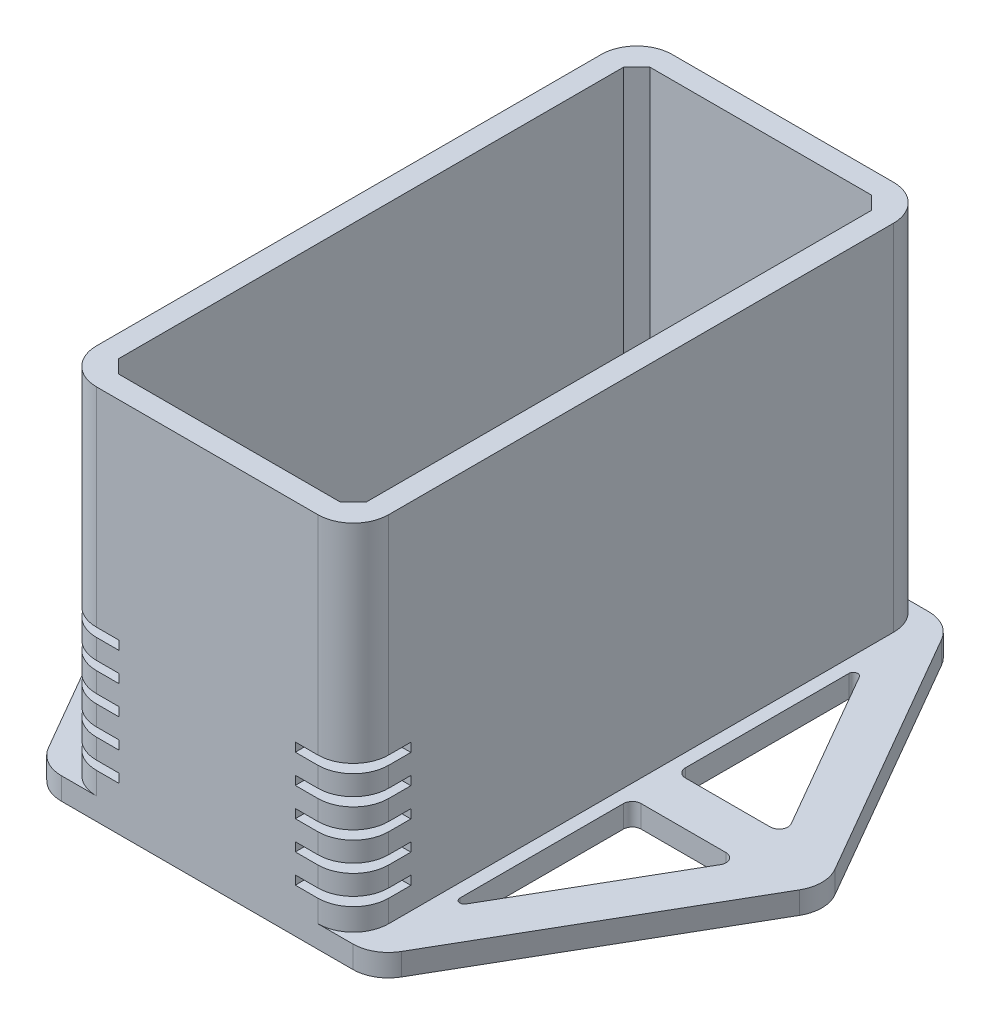
SolidWorks part; units mm, degrees
ref_plane "Front Plane" through (0, 0, 0) normal (0, 0, 1) x (1, 0, 0)
ref_plane "Top Plane" through (0, 0, 0) normal (0, 1, 0) x (1, 0, 0)
ref_plane "Right Plane" through (0, 0, 0) normal (1, 0, 0) x (0, 0, -1)
sketch "Sketch1" plane through (0, 0, 0) normal (0, 1, 0) x (1, 0, 0)
  line L1 (-75.0555, 0) -> (-37.5278, -65)
  line L2 (-37.5278, -65) -> (37.5278, -65)
  line L3 (37.5278, -65) -> (75.0555, 0)
  line L4 (75.0555, 0) -> (37.5278, 65)
  line L5 (37.5278, 65) -> (-37.5278, 65)
  line L6 (-37.5278, 65) -> (-75.0555, 0)
  circle A0 centre (0, 0) radius 65 construction
  circle A1 centre (0, 0) radius 50 construction
  dimension "D2" = 100
  dimension "D1" = 130
extrude "Boss-Extrude1" add sketch "Sketch1" along normal blind 5
fillet "Fillet1" radius 8 6 edges at (37.5278, 2.5, -65) (75.0555, 2.5, 0) (37.5278, 2.5, 65) (-37.5278, 2.5, 65) (-75.0555, 2.5, 0) (-37.5278, 2.5, -65)
sketch "Sketch3" plane through (0, 5, 0) normal (0, 1, 0) x (1, 0, 0)
  line L0 (-32.909, -65) -> (32.909, -65) construction
  line L1 (-25, 65) -> (25, 65)
  line L2 (-33, 57) -> (-33, -57)
  line L3 (-25, -65) -> (25, -65)
  line L4 (33, 57) -> (33, -57)
  line L5 (-33, 65) -> (33, -65) construction
  line L6 (-33, -65) -> (33, 65) construction
  arc A0 (33, 57) -> (25, 65) centre (25, 57) ccw
  arc A1 (33, -57) -> (25, -65) centre (25, -57) cw
  arc A2 (-25, -65) -> (-33, -57) centre (-25, -57) cw
  arc A3 (-25, 65) -> (-33, 57) centre (-25, 57) ccw
  point P0 (0, 0)
  dimension "D1" = 8
  dimension "D2" = 50
extrude "Boss-Extrude2" add sketch "Sketch3" along normal blind 80
sketch "Sketch4" plane through (0, 85, 0) normal (0, 1, 0) x (1, 0, 0)
  line L0 (-28, 57) -> (-25, 60)
  line L1 (25, 60) -> (28, 57)
  line L2 (28, -57) -> (25, -60)
  line L3 (-28, -57) -> (-25, -60)
  line L9 (-25, -60) -> (25, -60)
  line L10 (28, -57) -> (28, 57)
  line L11 (25, 60) -> (-25, 60)
  line L12 (-28, 57) -> (-28, -57)
  line L13 (-25, -60) -> (25, -60)
  line L14 (28, -57) -> (28, 57)
  line L15 (25, 60) -> (-25, 60)
  line L16 (-28, 57) -> (-28, -57)
  arc A9 (-28, -57) -> (-25, -60) centre (-25, -57) ccw
  arc A10 (25, -60) -> (28, -57) centre (25, -57) ccw
  arc A11 (28, 57) -> (25, 60) centre (25, 57) ccw
  arc A12 (-25, 60) -> (-28, 57) centre (-25, 57) ccw
  dimension "D1" = 5
extrude "Cut-Extrude1" cut sketch "Sketch4" against normal up to surface (85 mm away) up to face at (0, 0, 0)
sketch "Sketch8" plane through (0, 0, 0) normal (0, 1, 0) x (1, 0, 0)
  line L0 (0, 40) -> (0, 25) construction
  line L1 (0, 55) -> (0, 65) construction
  line L2 (9.5263, 26.5) -> (24.2487, 52) construction
  line L3 (22.5167, 55) -> (-22.5167, 55) construction
  line L4 (-24.2487, 52) -> (-9.5263, 26.5) construction
  line L5 (-12.5, 0) -> (-62.3346, 0) construction
  line L36 (6.9282, 25) -> (-6.9282, 25) construction
  line L37 (27.7128, 5) -> (57.1577, 5) construction
  line L38 (58.8897, 8) -> (36.3731, 47) construction
  line L39 (32.909, 47) -> (18.1865, 21.5) construction
  line L40 (25.1147, 6.5) -> (18.1865, 18.5) construction
  line L41 (18.1865, -21.5) -> (32.909, -47) construction
  line L42 (36.3731, -47) -> (58.8897, -8) construction
  line L43 (57.1577, -5) -> (27.7128, -5) construction
  line L44 (18.1865, -18.5) -> (25.1147, -6.5) construction
  line L45 (-9.5263, -26.5) -> (-24.2487, -52) construction
  line L46 (-22.5167, -55) -> (22.5167, -55) construction
  line L47 (24.2487, -52) -> (9.5263, -26.5) construction
  line L48 (-6.9282, -25) -> (6.9282, -25) construction
  line L49 (-27.7128, -5) -> (-57.1577, -5) construction
  line L50 (-58.8897, -8) -> (-36.3731, -47) construction
  line L51 (-32.909, -47) -> (-18.1865, -21.5) construction
  line L52 (-25.1147, -6.5) -> (-18.1865, -18.5) construction
  line L53 (-18.1865, 21.5) -> (-32.909, 47) construction
  line L54 (-37.866, 44.4141) -> (-58.8897, 8)
  line L55 (-57.1577, 5) -> (-38, 5)
  line L56 (-18.1865, 18.5) -> (-25.1147, 6.5) construction
  line L57 (-36, 7) -> (-36, 43.9141)
  line L58 (-33, 57) -> (-33, -57) construction
  line L59 (-36, -7) -> (-36, -43.9141)
  line L60 (-36.3731, 47) -> (-36, 47.6462) construction
  line L61 (-36, 5) -> (-27.7128, 5) construction
  line L71 (-33, 57) -> (-33, -57) construction
  line L72 (-57.1577, -5) -> (-38, -5)
  line L73 (-37.866, -44.4141) -> (-58.8897, -8)
  line L74 (37.866, -44.4141) -> (58.8897, -8)
  line L75 (57.1577, -5) -> (38, -5)
  line L76 (36, -7) -> (36, -43.9141)
  line L77 (36, 7) -> (36, 43.9141)
  line L78 (57.1577, 5) -> (38, 5)
  line L79 (37.866, 44.4141) -> (58.8897, 8)
  circle A0 centre (0, 0) radius 12.5 construction
  circle A1 centre (0, 40) radius 15 construction
  arc A3 (-22.5167, 55) -> (-24.2487, 52) centre (-22.5167, 53) ccw
  arc A4 (24.2487, 52) -> (22.5167, 55) centre (22.5167, 53) ccw construction
  arc A5 (6.9282, 25) -> (9.5263, 26.5) centre (6.9282, 28) ccw construction
  arc A6 (-6.9282, 25) -> (-9.5263, 26.5) centre (-6.9282, 28) cw construction
  arc A7 (25.1147, 6.5) -> (27.7128, 5) centre (27.7128, 8) ccw construction
  arc A8 (57.1577, 5) -> (58.8897, 8) centre (57.1577, 7) ccw construction
  arc A9 (36.3731, 47) -> (32.909, 47) centre (34.641, 46) ccw construction
  arc A10 (18.1865, 18.5) -> (18.1865, 21.5) centre (20.7846, 20) cw construction
  arc A11 (18.1865, -18.5) -> (18.1865, -21.5) centre (20.7846, -20) ccw construction
  arc A12 (32.909, -47) -> (36.3731, -47) centre (34.641, -46) ccw construction
  arc A13 (58.8897, -8) -> (57.1577, -5) centre (57.1577, -7) ccw construction
  arc A14 (25.1147, -6.5) -> (27.7128, -5) centre (27.7128, -8) cw construction
  arc A15 (-6.9282, -25) -> (-9.5263, -26.5) centre (-6.9282, -28) ccw construction
  arc A16 (-24.2487, -52) -> (-22.5167, -55) centre (-22.5167, -53) ccw construction
  arc A17 (22.5167, -55) -> (24.2487, -52) centre (22.5167, -53) ccw construction
  arc A18 (6.9282, -25) -> (9.5263, -26.5) centre (6.9282, -28) cw construction
  arc A19 (-25.1147, -6.5) -> (-27.7128, -5) centre (-27.7128, -8) ccw construction
  arc A20 (-57.1577, -5) -> (-58.8897, -8) centre (-57.1577, -7) ccw construction
  arc A21 (-36.3731, -47) -> (-32.909, -47) centre (-34.641, -46) ccw construction
  arc A22 (-18.1865, -18.5) -> (-18.1865, -21.5) centre (-20.7846, -20) cw construction
  arc A23 (-18.1865, 18.5) -> (-18.1865, 21.5) centre (-20.7846, 20) ccw construction
  arc A24 (-32.909, 47) -> (-36.3731, 47) centre (-34.641, 46) ccw construction
  arc A25 (-58.8897, 8) -> (-57.1577, 5) centre (-57.1577, 7) ccw
  arc A26 (-25.1147, 6.5) -> (-27.7128, 5) centre (-27.7128, 8) cw construction
  arc A28 (57.1577, -5) -> (58.8897, -8) centre (57.1577, -7) cw construction
  arc A31 (-36, 7) -> (-38, 5) centre (-38, 7) cw
  arc A32 (-36, 43.9141) -> (-37.866, 44.4141) centre (-37, 43.9141) ccw
  arc A33 (-36, -43.9141) -> (-37.866, -44.4141) centre (-37, -43.9141) cw
  arc A34 (-36, -7) -> (-38, -5) centre (-38, -7) ccw
  arc A35 (-58.8897, -8) -> (-57.1577, -5) centre (-57.1577, -7) cw
  arc A36 (57.1577, -5) -> (58.8897, -8) centre (57.1577, -7) cw construction
  arc A37 (58.8897, -8) -> (57.1577, -5) centre (57.1577, -7) ccw
  arc A38 (36, -7) -> (38, -5) centre (38, -7) cw
  arc A39 (36, -43.9141) -> (37.866, -44.4141) centre (37, -43.9141) ccw
  arc A40 (36, 43.9141) -> (37.866, 44.4141) centre (37, 43.9141) cw
  arc A41 (36, 7) -> (38, 5) centre (38, 7) ccw
  arc A42 (58.8897, 8) -> (57.1577, 5) centre (57.1577, 7) cw
  point P19 (0, 25)
  point P30 (0, 0)
  point P66 (0, 0)
  point P88 (0, 0)
  point P90 (0, 0)
  dimension "D1" = 25
  dimension "D3" = 30
  dimension "D6" = 2
  dimension "D8" = 3
  dimension "D11" = 2
  dimension "D12" = 1
  dimension "D2" = 40
  dimension "D4" = 10
  dimension "D5" = 15
  dimension "D7" = 25
  dimension "D9" = 3
extrude "Cut-Extrude2" cut sketch "Sketch8" along normal up to surface (5 mm away) contours A32 | L54 A25 L55 L57 | A35 L73 A33 L59 A34 L72 | L76 A39 L74 A37 L75 A38 | A42 L79 A40 L77 A41 L78 region at (-44.1761, 0, -19.1857) region at (-44.1761, 0, 19.1857) region at (44.1761, 0, 19.1857) region at (44.1761, 0, -19.1857) up to face at (-41.2442, 5, 0)
ref_plane "Plane1" through (0, 10, 0) normal (0, 1, 0) x (1, 0, 0)
sketch "Sketch9" plane through (0, 10, 0) normal (0, 1, 0) x (1, 0, 0)
  line L0 (-32.909, -65) -> (-33.909, -65) construction
  line L6 (-33.909, -65) -> (-19.909, -65)
  line L7 (-33.909, -65) -> (-33.909, -52)
  line L8 (-33.909, -52) -> (-19.909, -52)
  line L9 (-19.909, -65) -> (-19.909, -52)
  line L10 (-33.909, -65) -> (-19.909, -52) construction
  line L11 (-33.909, -52) -> (-19.909, -65) construction
  point P7 (-26.909, -58.5)
  dimension "D1" = 1
  dimension "D2" = 13
  dimension "D3" = 14
extrude "Cut-Extrude3" cut sketch "Sketch9" along normal blind 2
pattern_linear "LPattern1" count 5 spacing 6.5 along (0, 1, 0) of "Cut-Extrude3"
mirror "Mirror1" about plane through (0, 0, 0) normal (1, 0, 0) of "LPattern1"
